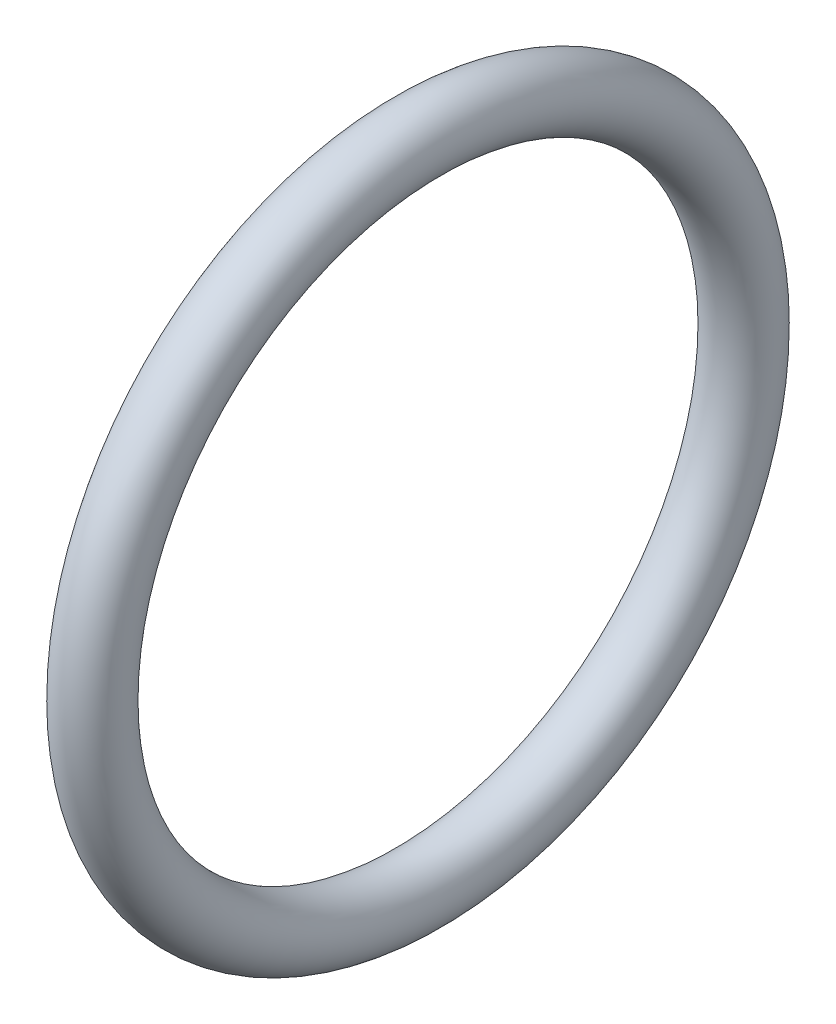
SolidWorks part; units mm, degrees
ref_plane "Plano frontal" through (0, 0, 0) normal (0, 0, 1) x (1, 0, 0)
ref_plane "Plano superior" through (0, 0, 0) normal (0, 1, 0) x (1, 0, 0)
ref_plane "Plano direito" through (0, 0, 0) normal (1, 0, 0) x (0, 0, -1)
sketch "Esboço1" plane through (0, 0, 0) normal (0, 0, 1) x (1, 0, 0)
  line L0 (0, 0) -> (0, 12.1) construction
  line L1 (0, 0) -> (21.9936, 0) construction
  circle A0 centre (0, 12.1) radius 1.2
  dimension "D1" = 2.4
  dimension "D2" = 12.1
revolve "Revolução1" add sketch "Esboço1" angle 360 about L1
ref_axis "Eixo1" through (5.625, 0, 0) along (-1, 0, 0)
